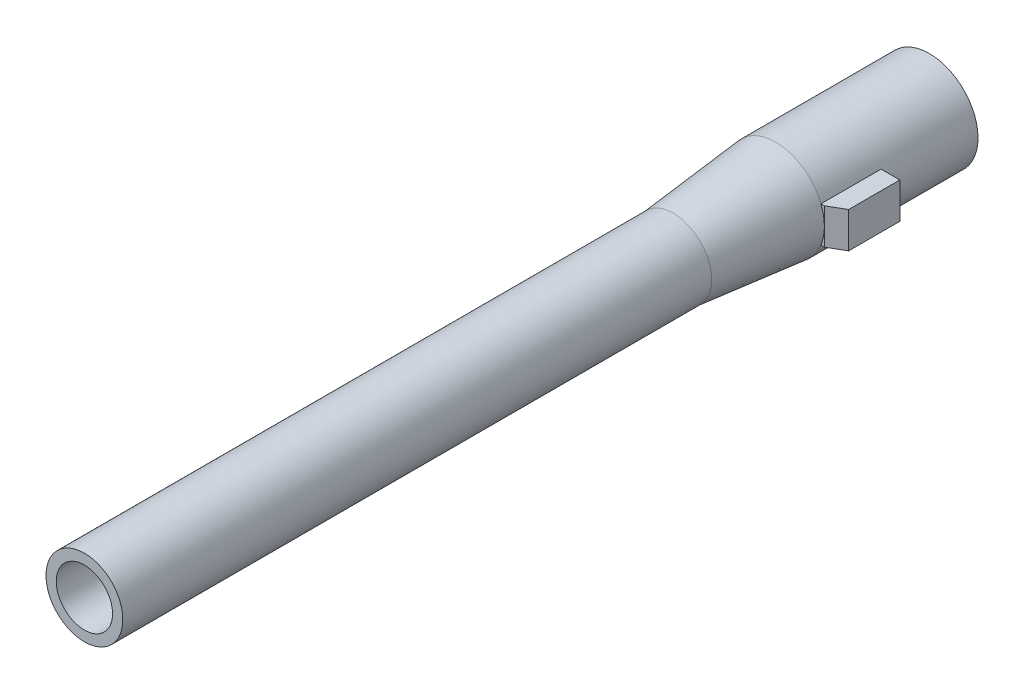
SolidWorks part; units mm, degrees
material "ABS"
ref_plane "Front Plane" through (0, 0, 0) normal (0, 0, 1) x (1, 0, 0)
ref_plane "Top Plane" through (0, 0, 0) normal (0, 1, 0) x (1, 0, 0)
ref_plane "Right Plane" through (0, 0, 0) normal (1, 0, 0) x (0, 0, -1)
sketch "Sketch1" plane through (0, 0, 0) normal (0, 0, 1) x (1, 0, 0)
  circle A0 centre (0, 0) radius 9.5
  circle A1 centre (0, 0) radius 7.6
  dimension "D1" = 19
  dimension "D2" = 15.2
extrude "Boss-Extrude1" add sketch "Sketch1" along normal blind 30
sketch "Sketch4" plane through (0, 0, 0) normal (1, 0, 0) x (0, 0, -1)
  line L0 (-30, 0) -> (-43.4411, 0)
  line L1 (-30, 9.5) -> (-30, -9.5) construction
  line L2 (-142.8078, 5) -> (-30, 5.75)
  line L3 (-30, 9.5) -> (-30, 5.75)
  line L5 (-142.8078, 5) -> (-165, 5.5)
  line L6 (-50, 7.5) -> (-30, 9.5)
  line L7 (-165, 5.5) -> (-165, 7.5)
  line L8 (-165, 7.5) -> (-142.8078, 7.5)
  line L9 (-142.8078, 7.5) -> (-50, 7.5)
  dimension "D4" = 2
revolve "Revolve1" add sketch "Sketch4" angle 360 about L0 region at (0, 6.5298, 96.5784)
sketch "Sketch7" plane through (0, 0, 0) normal (0, 1, 0) x (1, 0, 0)
  line L0 (9.5, -18.2679) -> (7.6, -18.2679)
  line L1 (7.6, -30) -> (7.6, 0) construction
  line L2 (7.6, -18.2679) -> (7.6, -30)
  line L3 (12.5, -28.2679) -> (12.5, -18.2679)
  line L4 (9.5, -30) -> (12.5, -28.2679)
  line L5 (12.5, -18.2679) -> (9.5, -18.2679)
  line L6 (9.5, -30) -> (9.5, 0) construction
  line L8 (7.6, -30) -> (9.5, -30)
  dimension "D3" = 10
extrude "Boss-Extrude4" add sketch "Sketch7" along normal blind 3.5 and the other way blind 3.5
sketch "Sketch8" plane through (0, 0, 0) normal (1, 0, 0) x (0, 0, -1)
  line L0 (-30, 7.6) -> (-31.8624, 5.7376)
  line L1 (-30, 5.75) -> (-142.8078, 5) construction
  line L2 (-31.8624, 5.7376) -> (-30, 5.75)
  line L3 (-30, 5.75) -> (-30, 7.6)
  line L4 (-30, 7.6) -> (-30.0071, 7.5753)
  line L5 (-30, 0) -> (-31.3425, 0)
revolve "Cut-Revolve1" cut sketch "Sketch8" angle 360 about L5
